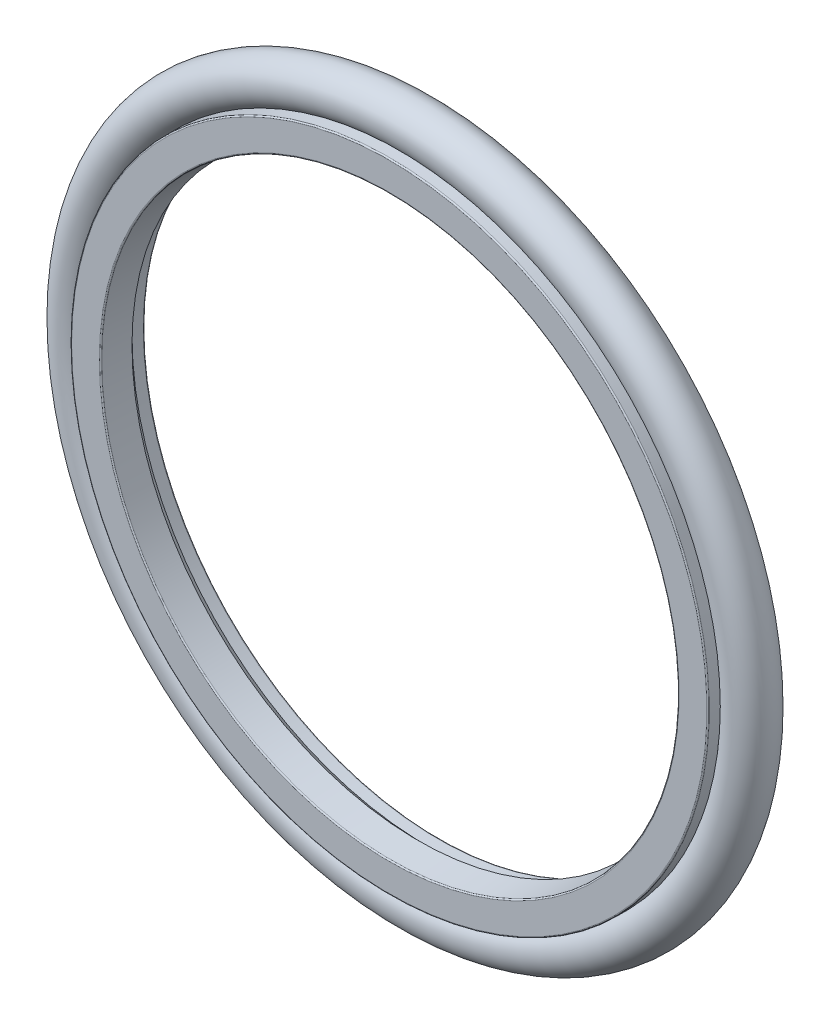
SolidWorks part; units mm, degrees
material "PTFE+NBR"
ref_plane "Front Plane" through (0, 0, 0) normal (0, 0, 1) x (1, 0, 0)
ref_plane "Top Plane" through (0, 0, 0) normal (0, 1, 0) x (1, 0, 0)
ref_plane "Right Plane" through (0, 0, 0) normal (1, 0, 0) x (0, 0, -1)
sketch "Sketch1" plane through (0, 0, 0) normal (1, 0, 0) x (0, 0, -1)
  line L0 (0, 23.55) -> (0, 25.25)
  line L1 (-0.1, 25.35) -> (-3.9, 25.35)
  line L2 (-4, 25.25) -> (-4, 23.0417)
  line L3 (-3.9087, 22.9421) -> (-1.7, 22.75)
  line L5 (-1, 23.45) -> (-1.7, 22.75)
  line L6 (0, 0) -> (-16.4728, 0) construction
  line L7 (-0.1, 23.45) -> (-1, 23.45)
  arc A0 (-0.1, 25.35) -> (0, 25.25) centre (-0.1, 25.25) cw
  arc A1 (0, 23.55) -> (-0.1, 23.45) centre (-0.1, 23.55) cw
  arc A3 (-4, 23.0417) -> (-3.9087, 22.9421) centre (-3.9, 23.0417) ccw
  arc A4 (-3.9, 25.35) -> (-4, 25.25) centre (-3.9, 25.25) ccw
  point P19 (-4, 22.95)
  point P22 (-4, 25.35)
  dimension "D2" = 0.1
  dimension "D4" = 1
  dimension "D10" = 0.1
  dimension "D7" = 2.3
  dimension "D8" = 0.1
  dimension "D1" = 4
  dimension "D3" = 50.7
  dimension "D5" = 1.9
  dimension "D6" = 2.4
  dimension "D9" = 2.6
  dimension "D11" = 45.5
  dimension "D12" = 45.9
  dimension "D13" = 46.9
revolve "Revolve1" add sketch "Sketch1" angle 360 about L6
sketch "Sketch4" plane through (0, 0, 0) normal (1, 0, 0) x (0, 0, -1)
  line L0 (0, 0) -> (-3.9, 0) construction
  line L1 (-3.9, 25.35) -> (-3.9, -25.35) construction
  line L2 (-1.95, 0) -> (-1.95, 52.8756) construction
  circle A0 centre (-1.95, 26.765) radius 1.765
  dimension "D1" = 50
  dimension "D2" = 3.53
revolve "Revolve2" add sketch "Sketch4" angle 360 about L0
ref_axis "Axis1" through (0, 0, 0) along (0, 0, 1)
